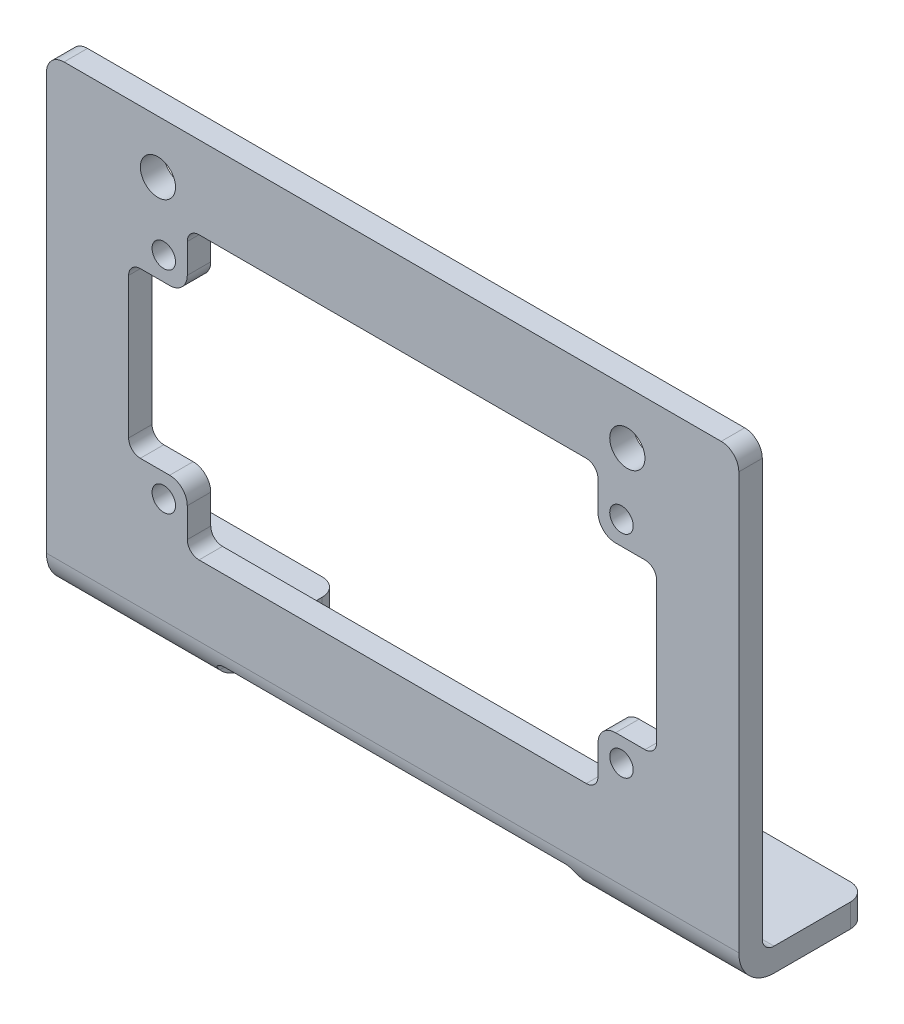
SolidWorks part; units mm, degrees
ref_plane "Front Plane" through (0, 0, 0) normal (0, 0, 1) x (1, 0, 0)
ref_plane "Top Plane" through (0, 0, 0) normal (0, 1, 0) x (1, 0, 0)
ref_plane "Right Plane" through (0, 0, 0) normal (1, 0, 0) x (0, 0, -1)
sketch "Sketch1" plane through (0, 0, 0) normal (0, 0, 1) x (1, 0, 0)
  line L0 (0, -55) -> (0, 55) construction
  line L1 (29.5, -20) -> (-29.5, -20) construction
  line L2 (29.5, -20) -> (29.5, 20) construction
  line L3 (29.5, 20) -> (-29.5, 20) construction
  line L4 (-29.5, -20) -> (-29.5, 20) construction
  line L5 (29.5, -20) -> (-29.5, 20) construction
  line L6 (29.5, 20) -> (-29.5, -20) construction
  line L11 (15.5, -18) -> (-15.5, -18) construction
  line L12 (15.5, -18) -> (15.5, -20) construction
  line L13 (15.5, -20) -> (-15.5, -20) construction
  line L14 (-15.5, -18) -> (-15.5, -20) construction
  line L15 (15.5, -18) -> (-15.5, -20) construction
  line L16 (15.5, -20) -> (-15.5, -18) construction
  line L17 (-22.5, 8) -> (-17.5, 8)
  line L18 (22.5, 13) -> (-22.5, 13) construction
  line L19 (22.5, 13) -> (22.5, -11) construction
  line L20 (22.5, -11) -> (-22.5, -11) construction
  line L21 (-22.5, 13) -> (-22.5, -11) construction
  line L22 (22.5, 13) -> (-22.5, -11) construction
  line L23 (22.5, -11) -> (-22.5, 13) construction
  line L24 (-17.5, 8) -> (-17.5, 13)
  line L25 (-5.0155, 1) -> (4.7745, 1) construction
  line L26 (-22.5, -6) -> (-17.5, -6)
  line L27 (-17.5, -6) -> (-17.5, -11)
  line L28 (-17.5, 13) -> (17.5, 13)
  line L29 (-22.5, 8) -> (-22.5, -6)
  line L30 (-17.5, -11) -> (17.5, -11)
  line L31 (-15.5, -18) -> (15.5, -18)
  line L32 (-15.5, -20) -> (-29.5, -20)
  line L33 (-29.5, -20) -> (-29.5, 20)
  line L34 (-29.5, 20) -> (29.5, 20)
  line L35 (-15.5, -18) -> (-15.5, -20)
  line L36 (5.0155, 1) -> (-4.7745, 1) construction
  line L37 (-22.5, -11) -> (22.5, 13) construction
  line L38 (-22.5, 13) -> (22.5, -11) construction
  line L39 (22.5, 13) -> (22.5, -11) construction
  line L40 (-15.5, -20) -> (15.5, -18) construction
  line L41 (-15.5, -18) -> (15.5, -20) construction
  line L42 (15.5, -18) -> (15.5, -20) construction
  line L43 (-29.5, 20) -> (29.5, -20) construction
  line L44 (-29.5, -20) -> (29.5, 20) construction
  line L45 (29.5, -20) -> (29.5, 20) construction
  line L46 (15.5, -18) -> (15.5, -20)
  line L47 (29.5, -20) -> (29.5, 20)
  line L48 (15.5, -20) -> (29.5, -20)
  line L49 (22.5, 8) -> (22.5, -6)
  line L50 (17.5, -6) -> (17.5, -11)
  line L51 (22.5, -6) -> (17.5, -6)
  line L52 (17.5, 8) -> (17.5, 13)
  line L53 (22.5, 8) -> (17.5, 8)
  circle A0 centre (-19.5, 10) radius 1
  circle A1 centre (-20, 15.5) radius 1.5
  circle A2 centre (-19.5, -8) radius 1
  circle A3 centre (19.5, -8) radius 1
  circle A4 centre (20, 15.5) radius 1.5
  circle A5 centre (19.5, 10) radius 1
  point P0 (0, 0)
  point P7 (0, -19)
  point P15 (0, 1)
  point P36 (0, -18)
  point P44 (0, 20)
  point P45 (0, -11)
  point P48 (0, 13)
  dimension "D12" = 2
  dimension "D14" = 3
  dimension "D1" = 40
  dimension "D2" = 59
  dimension "D3" = 31
  dimension "D4" = 2
  dimension "D5" = 7
  dimension "D6" = 7
  dimension "D7" = 7
  dimension "D8" = 5
  dimension "D9" = 5
  dimension "D10" = 10
  dimension "D11" = 10
  dimension "D13" = 9.5
  dimension "D15" = 4.5
extrude "Boss-Extrude1" add sketch "Sketch1" along normal blind 2
sketch "Sketch4" plane through (0, -20, 0) normal (0, -1, 0) x (1, 0, 0)
  line L0 (-15.5, 2) -> (-15.5, 0) construction
  line L1 (-29.5, 2) -> (-15.5, 2) construction
  line L2 (-29.5, 2) -> (-29.5, 0) construction
  line L3 (-15.5, 2) -> (-15.5, 0)
  line L4 (-29.5, 2) -> (-15.5, 2)
  line L5 (-29.5, 2) -> (-29.5, 0)
  line L6 (-29.5, 0) -> (-29.5, -9)
  line L7 (-29.5, -9) -> (-15.5, -9)
  line L8 (-15.5, -9) -> (-15.5, 0)
  line L9 (0, -55) -> (0, 55) construction
  line L10 (15.5, -9) -> (15.5, 0)
  line L11 (29.5, -9) -> (15.5, -9)
  line L12 (29.5, 0) -> (29.5, -9)
  line L13 (29.5, 2) -> (29.5, 0)
  line L14 (29.5, 2) -> (15.5, 2)
  line L15 (15.5, 2) -> (15.5, 0)
  circle A0 centre (-20, -4) radius 1.5
  circle A1 centre (20, -4) radius 1.5
  dimension "D4" = 3
  dimension "D1" = 11
  dimension "D2" = 4.5
  dimension "D3" = 5
extrude "Boss-Extrude2" add sketch "Sketch4" against normal up to surface (2 mm away) up to face at (0, -18, 1)
fillet "Fillet2" radius 1.5 10 edges at (-29.5, -19, -9) (15.5, -19, -9) (-15.5, -19, -9) (29.5, -19, -9) (17.5, -6, 1) (-17.5, -6, 1) (-17.5, 8, 1) (17.5, 8, 1) (-29.5, 20, 1) (29.5, 20, 1)
fillet "Fillet3" radius 1 10 edges at (15.5, -18, 1) (-15.5, -18, 1) (-22.5, 8, 1) (-17.5, 13, 1) (-22.5, -6, 1) (-17.5, -11, 1) (17.5, -11, 1) (17.5, 13, 1) (22.5, 8, 1) (22.5, -6, 1)
fillet "Fillet4" radius 1 2 edges at (-22.5, -18, 0) (22.5, -18, 0)
fillet "Fillet5" radius 3 1 edges at (22.5, -20, 2)
